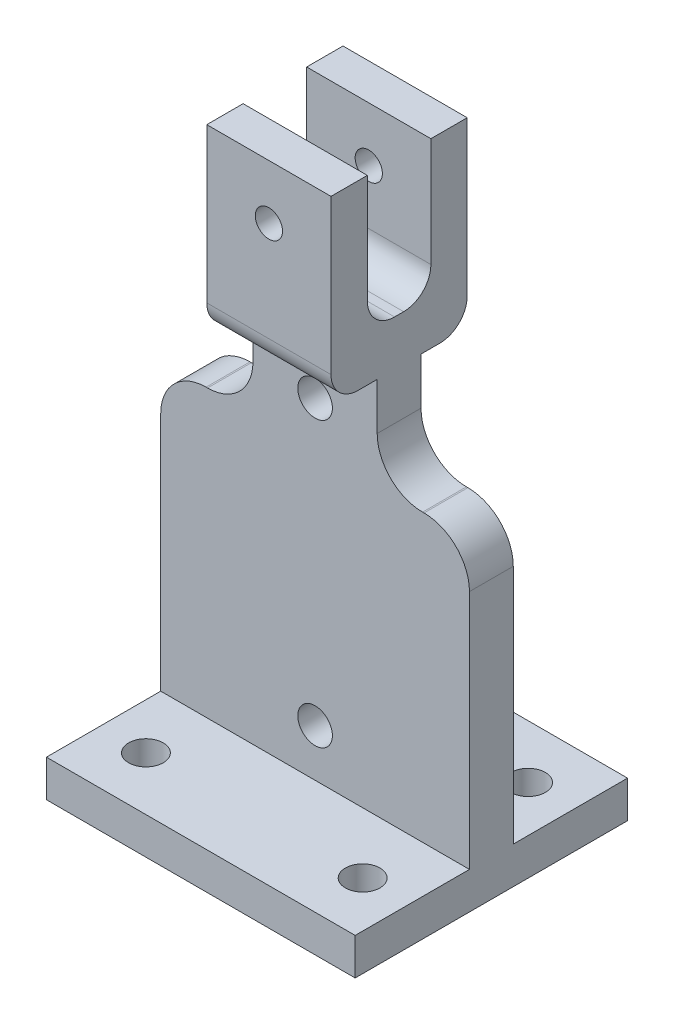
SolidWorks part; units mm, degrees
ref_plane "Front Plane" through (0, 0, 0) normal (0, 0, 1) x (1, 0, 0)
ref_plane "Top Plane" through (0, 0, 0) normal (0, 1, 0) x (1, 0, 0)
ref_plane "Right Plane" through (0, 0, 0) normal (1, 0, 0) x (0, 0, -1)
sketch "Sketch1" plane through (0, 0, 0) normal (0, 0, 1) x (1, 0, 0)
  line L0 (-17, 0) -> (17, 0)
  line L1 (17, 0) -> (17, 31.496)
  line L3 (6.84, 41.656) -> (-6.84, 41.656)
  line L4 (17, 31.496) -> (17, 41.656) construction
  line L5 (17, 41.656) -> (6.84, 41.656) construction
  line L6 (0, -55) -> (0, 55) construction
  line L7 (-17, 0) -> (-17, 31.496)
  line L9 (0, 0) -> (0, 5.207) construction
  line L10 (17, 31.496) -> (6.84, 31.496)
  line L11 (6.84, 31.496) -> (6.84, 41.656)
  line L12 (-6.84, 41.656) -> (-6.84, 31.496)
  line L13 (-6.84, 31.496) -> (-17.5151, 31.496)
  circle A0 centre (0, 5.207) radius 1.905
  circle A1 centre (0, 36.449) radius 1.905
  point P4 (0, 0)
  point P11 (0, 0)
  point P13 (0, 41.656)
  dimension "D5" = 3.81
  dimension "D7" = 2
  dimension "D1" = 34
  dimension "D2" = 41.656
  dimension "D3" = 10.16
  dimension "D4" = 10.16
  dimension "D6" = 5.207
  dimension "D8" = 5.207
extrude "Boss-Extrude1" add sketch "Sketch1" along normal mid plane 4.826 contours L12 L13 L7 L0 L1 L10 L11 L3 A1 A0 | L3 region at (0, 18.0891, 0)
sketch "Sketch3" plane through (0, 0, 0) normal (0, 1, 0) x (1, 0, 0)
  line L0 (0, 0) -> (-11.935, 0) construction
  line L1 (-17, -15) -> (17, -15)
  line L2 (-17, -15) -> (-17, 15)
  line L3 (-17, 15) -> (17, 15)
  line L4 (17, -15) -> (17, 15)
  line L5 (-17, -15) -> (17, 15) construction
  line L6 (-17, 15) -> (17, -15) construction
  line L7 (-11.935, 0) -> (-11.935, -9.11) construction
  line L8 (0, 0) -> (0, 8.8012) construction
  circle A0 centre (-11.935, -9.11) radius 1.905
  circle A1 centre (11.935, -9.11) radius 1.905
  circle A2 centre (11.935, 9.11) radius 1.905
  circle A3 centre (-11.935, 9.11) radius 1.905
  point P0 (0, 0)
  dimension "D5" = 3.81
  dimension "D1" = 34
  dimension "D2" = 30
  dimension "D3" = 11.935
  dimension "D4" = 9.11
  dimension "D6" = 2
  dimension "D7" = 2
extrude "Boss-Extrude2" add sketch "Sketch3" against normal blind 4.064
fillet "Fillet1" radius 5 4 edges at (-17, 31.496, 0) (17, 31.496, 0) (-6.84, 31.496, 0) (6.84, 31.496, 0)
sketch "Sketch5" plane through (0, 41.656, 0) normal (0, 1, 0) x (1, 0, 0)
  line L0 (-6.84, 7.5) -> (-6.84, -7.5)
  line L1 (-6.84, -7.5) -> (6.84, -7.5)
  line L2 (6.84, -7.5) -> (6.84, 7.5)
  line L3 (6.84, 7.5) -> (-6.84, 7.5)
  line L4 (-6.84, -2.413) -> (-6.84, 2.413) construction
  line L5 (6.84, -2.413) -> (6.84, 2.413) construction
  line L6 (-6.84, -3.5) -> (6.84, -3.5)
  line L7 (-6.84, 3.5) -> (6.84, 3.5)
  point P9 (6.84, 0)
  line M7 (6.84, 2.413) -> (-6.84, 2.413)
  line M8 (-6.84, 2.413) -> (-6.84, -2.413)
  line M9 (-6.84, -2.413) -> (6.84, -2.413)
  line M10 (6.84, -2.413) -> (6.84, 2.413)
  dimension "D1" = 15
  dimension "D2" = 7.5
  dimension "D3" = 4
  dimension "D4" = 4
extrude "Boss-Extrude4" add sketch "Sketch5" along normal blind 5 contours M10 M7 M8 M9 | L0 L6 L2 M9 | L7 L0 L2 M7 region at (0, 41.656, -2.9565) region at (0, 41.656, 0) region at (0, 41.656, 2.9565)
extrude "Boss-Extrude5" add sketch "Sketch5<3>" along normal blind 20 contours L6 L0 L1 L2 | L0 L7 L2 L3 region at (0, 41.656, -5.5) region at (0, 41.656, 5.5)
sketch "Sketch5<3>" plane through (0, 41.656, 0) normal (0, 1, 0) x (1, 0, 0) same geometry as "Sketch5"
sketch "Sketch6" plane through (0, 0, -7.5) normal (0, 0, -1) x (-1, 0, 0)
  line L0 (-6.84, 61.656) -> (6.84, 61.656) construction
  circle A0 centre (0, 55.656) radius 1.5
  point P4 (0, 61.656)
  dimension "D1" = 3
  dimension "D2" = 6
extrude "Cut-Extrude1" cut sketch "Sketch6" against normal up to surface (15 mm away) up to face at (0, 51.656, 7.5)
fillet "Fillet2" radius 3 4 edges at (0, 41.656, 7.5) (0, 46.656, 3.5) (0, 46.656, -3.5) (0, 41.656, -7.5)
